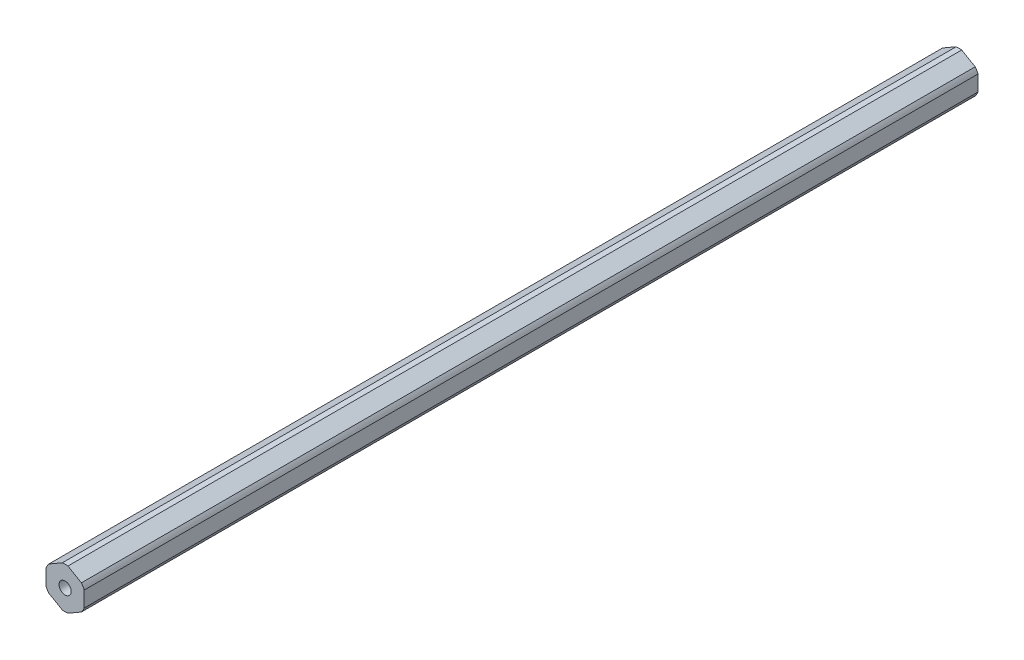
SolidWorks part; units mm, degrees
ref_plane "Front Plane" through (0, 0, 0) normal (0, 0, 1) x (1, 0, 0)
ref_plane "Top Plane" through (0, 0, 0) normal (0, 1, 0) x (1, 0, 0)
ref_plane "Right Plane" through (0, 0, 0) normal (1, 0, 0) x (0, 0, -1)
sketch "Sketch1" plane through (0, 0, 0) normal (0, 0, 1) x (1, 0, 0)
  line L1 (0, 7.3323) -> (-6.35, 3.6662)
  line L2 (-6.35, 3.6662) -> (-6.35, -3.6662)
  line L3 (-6.35, -3.6662) -> (0, -7.3323)
  line L4 (0, -7.3323) -> (6.35, -3.6662)
  line L5 (6.35, -3.6662) -> (6.35, 3.6662)
  line L6 (6.35, 3.6662) -> (0, 7.3323)
  circle A0 centre (0, 0) radius 6.35 construction
  circle A1 centre (0, 0) radius 6.858
  dimension "D1" = 12.7
  dimension "D2" = 13.716
extrude "Boss-Extrude1" add sketch "Sketch1" along normal mid plane 297.053 contours L5 A1 L6 L1 L2 L3 L4 region at (0, 0, 0)
sketch "Sketch2" plane through (0, 0, 148.5265) normal (0, 0, 1) x (1, 0, 0)
  circle A0 centre (0, 0) radius 2.0193
  dimension "D1" = 4.0386
extrude "Cut-Extrude1" [suppressed] cut sketch "Sketch2" against normal through all
hole_wizard "#10-32 Tapped Hole1" positions "3DSketch1" profile "Sketch3" tap size "#10-32" standard "ANSI Inch"
sketch3d "3DSketch1"
  line L0 (0, 0, 148.5265) -> (0, 0, -148.5265) construction
  line L1 (0, 0, 148.5265) -> (0, 0, -148.5265) construction
  point P0 (0, 0, -148.5265)
  point P4 (0, 0, 148.5265)
sketch "Sketch3" plane through (0, 0, -148.5265) normal (1, 0, 0) x (0, 1, 0)
  line L0 (0, 0) -> (0, 13.2428)
  line L1 (0, 13.2428) -> (2.0193, 12.0294)
  line L2 (2.0193, 12.0294) -> (2.0193, 0)
  line L5 (2.0193, 0) -> (0, 0)
  line L10 (0, 13.2428) -> (-2.0193, 12.0294) construction
  line L11 (0, -6.35) -> (0, 107.95) construction
  dimension "Tap Drill Dia." = 4.0386
  dimension "Tap Drill Depth" = 12.0294
  dimension "Drill Angle" = 118
cosmetic thread "Hole Thread1" parameters "D1"=9.652, "D2"=4.826
cosmetic thread "Hole Thread2" parameters "D1"=9.652, "D2"=4.826
